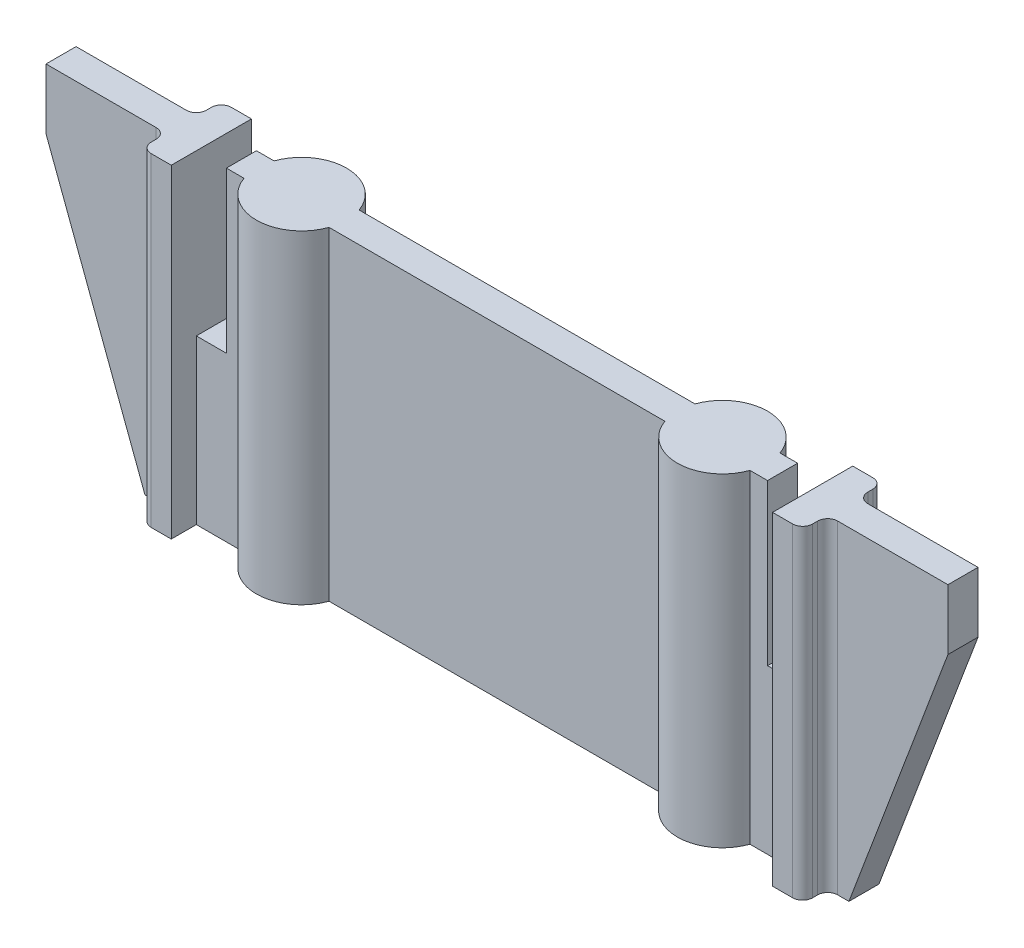
SolidWorks part; units mm, degrees
ref_plane "Front Plane" through (0, 0, 0) normal (0, 0, 1) x (1, 0, 0)
ref_plane "Top Plane" through (0, 0, 0) normal (0, 1, 0) x (1, 0, 0)
ref_plane "Right Plane" through (0, 0, 0) normal (1, 0, 0) x (0, 0, -1)
sketch "Sketch1" plane through (0, 0, 0) normal (0, 1, 0) x (1, 0, 0)
  line L0 (0, 0) -> (0, 10.4261) construction
  line L1 (-27, -17.5) -> (27, -17.5) construction
  line L2 (-27, -17.5) -> (-27, 11.1) construction
  line L3 (-27, 17.5) -> (27, 17.5) construction
  line L4 (27, -17.5) -> (27, 11.1) construction
  line L5 (-27, -17.5) -> (16.2, 10.5) construction
  line L6 (-27, 17.5) -> (-23.8664, 15.469) construction
  line L7 (-27, 11.1) -> (-27, 12.9) construction
  line L8 (-45, 13.5) -> (-25.2426, 13.5)
  line L9 (-45, 13.5) -> (-45, 10.5)
  line L10 (-45, 10.5) -> (-25.2426, 10.5)
  line L11 (45, 13.5) -> (45, 10.5)
  line L12 (-45, 13.5) -> (-25.4195, 12.8473) construction
  line L13 (-45, 10.5) -> (-25.4195, 11.1527) construction
  line L14 (-27, 12.9) -> (-27, 17.5) construction
  line L15 (-19.5181, 12.6506) -> (-16.6629, 10.8001) construction
  line L16 (-17.6087, 11.413) -> (27, -17.5) construction
  line L17 (-16.5339, 12.5511) -> (0, 12) construction
  line L18 (17.6087, 11.413) -> (16.5339, 11.4489) construction
  line L19 (0, 12) -> (16.5339, 12.5511) construction
  line L20 (25.4195, 12.8473) -> (45, 13.5) construction
  line L21 (16.6629, 10.8001) -> (19.5181, 12.6506) construction
  line L22 (19.5181, 12.6506) -> (20.8286, 13.5) construction
  line L23 (16.5339, 11.4489) -> (25.4195, 11.1527) construction
  line L24 (25.4195, 11.1527) -> (45, 10.5) construction
  line L25 (16.2, 10.5) -> (17.6087, 11.413) construction
  line L26 (17.6087, 11.413) -> (16.6629, 10.8001) construction
  line L27 (0, 12) -> (17.6087, 11.413) construction
  line L28 (-16.6629, 10.8001) -> (-17.6087, 11.413) construction
  line L29 (-25.2426, 10.5) -> (-16.7574, 10.5) construction
  line L30 (-16.7574, 10.5) -> (16.7574, 10.5)
  line L31 (-25.4195, 11.1527) -> (-16.5339, 11.4489) construction
  line L32 (-16.5339, 11.4489) -> (0, 12) construction
  line L33 (-25.4195, 12.8473) -> (-19.5181, 12.6506) construction
  line L34 (-19.5181, 12.6506) -> (-16.5339, 12.5511) construction
  line L35 (-25.2426, 13.5) -> (-20.8286, 13.5) construction
  line L36 (-16.7574, 13.5) -> (16.7574, 13.5)
  line L37 (-23.8664, 15.469) -> (-20.8286, 13.5) construction
  line L38 (-20.8286, 13.5) -> (-19.5181, 12.6506) construction
  line L39 (-20.8286, 13.5) -> (-16.7574, 13.5) construction
  line L40 (16.7574, 10.5) -> (10.6337, 10.5) construction
  line L41 (25.2426, 10.5) -> (45, 10.5)
  line L42 (16.5339, 12.5511) -> (19.5181, 12.6506) construction
  line L43 (16.7574, 13.5) -> (20.8286, 13.5) construction
  line L44 (25.2426, 13.5) -> (45, 13.5)
  line L45 (20.8286, 13.5) -> (23.8664, 15.469) construction
  line L46 (23.8664, 15.469) -> (27, 17.5) construction
  line L47 (20.8286, 13.5) -> (25.2426, 13.5) construction
  line L48 (19.5181, 12.6506) -> (45, 13.5) construction
  line L49 (27, 11.1) -> (27, 12.9) construction
  line L50 (27, 12.9) -> (27, 17.5) construction
  arc A0 (16.6629, 10.8001) -> (25.2426, 10.5) centre (21, 12) ccw construction
  arc A1 (-25.2426, 10.5) -> (-16.7574, 10.5) centre (-21, 12) ccw
  arc A2 (-25.4195, 12.8473) -> (-25.4195, 11.1527) centre (-21, 12) ccw construction
  arc A3 (-16.6629, 10.8001) -> (-16.5339, 11.4489) centre (-21, 12) ccw construction
  arc A4 (-16.7574, 13.5) -> (-25.2426, 13.5) centre (-21, 12) ccw
  arc A5 (16.5339, 12.5511) -> (16.6629, 10.8001) centre (21, 12) ccw construction
  arc A6 (16.7574, 13.5) -> (16.5339, 12.5511) centre (21, 12) ccw construction
  arc A7 (16.5339, 11.4489) -> (16.7574, 10.5) centre (21, 12) ccw construction
  arc A8 (16.7574, 10.5) -> (25.2426, 10.5) centre (21, 12) ccw
  arc A9 (-16.7574, 10.5) -> (-16.5339, 11.4489) centre (-21, 12) ccw construction
  arc A10 (-16.7574, 13.5) -> (-25.2426, 13.5) centre (-21, 12) ccw construction
  arc A11 (25.4195, 11.1527) -> (25.4195, 12.8473) centre (21, 12) ccw construction
  arc A12 (25.2426, 13.5) -> (16.7574, 13.5) centre (21, 12) ccw
  arc A13 (25.4195, 12.8473) -> (25.2426, 13.5) centre (21, 12) ccw construction
  arc A14 (25.2426, 10.5) -> (25.4195, 11.1527) centre (21, 12) ccw construction
  arc A15 (25.4195, 11.1527) -> (16.5339, 11.4489) centre (21, 12) ccw construction
  arc A16 (25.2426, 10.5) -> (25.4195, 11.1527) centre (21, 12) ccw construction
  arc A17 (-25.4195, 11.1527) -> (-25.2426, 10.5) centre (-21, 12) ccw construction
  arc A18 (-25.2426, 10.5) -> (-16.6629, 10.8001) centre (-21, 12) ccw construction
  arc A19 (-25.4195, 11.1527) -> (-25.2426, 10.5) centre (-21, 12) ccw construction
  arc A20 (-25.2426, 13.5) -> (-25.4195, 12.8473) centre (-21, 12) ccw construction
  arc A21 (-25.4195, 12.8473) -> (-25.4195, 11.1527) centre (-21, 12) ccw construction
  arc A22 (-25.2426, 13.5) -> (-25.4195, 12.8473) centre (-21, 12) ccw construction
  arc A23 (-16.5339, 11.4489) -> (-16.5339, 12.5511) centre (-21, 12) ccw construction
  arc A24 (-16.5339, 11.4489) -> (-16.5339, 12.5511) centre (-21, 12) ccw construction
  arc A25 (-16.5339, 12.5511) -> (-16.7574, 13.5) centre (-21, 12) ccw construction
  arc A26 (-16.5339, 12.5511) -> (-16.7574, 13.5) centre (-21, 12) ccw construction
  point P4 (0, 0)
  point P13 (0, 12)
  dimension "D1" = 9
  dimension "D2" = 3
  dimension "D3" = 54
  dimension "D4" = 35
  dimension "D5" = 42
  dimension "D6" = 90
  dimension "D7" = 12
extrude "Boss-Extrude1" add sketch "Sketch1" along normal blind 32.31 contours A4 L8 L9 L10 A1 L30 A8 L41 L11 L44 A12 L36
sketch "Sketch2" plane through (0, 0, -10.5) normal (0, 0, 1) x (1, 0, 0)
  line L0 (-35.1213, 0) -> (-45, 26.2724)
  line L1 (-45, 0) -> (-25.2426, 0) construction
  line L2 (-45, 32.31) -> (-45, 0) construction
  line L3 (-45, 26.2724) -> (-58.3904, 22.5254)
  line L4 (-58.3904, 22.5254) -> (-53.8147, -5.5007)
  line L5 (-53.8147, -5.5007) -> (-35.1213, -4.7634)
  line L6 (-35.1213, -4.7634) -> (-35.1213, 0)
  line L7 (0, 0) -> (0, 6.7705) construction
  line L8 (-16.7574, 0) -> (16.7574, 0) construction
  line L9 (53.8147, -5.5007) -> (35.1213, -4.7634)
  line L10 (58.3904, 22.5254) -> (53.8147, -5.5007)
  line L11 (45, 26.2724) -> (58.3904, 22.5254)
  line L12 (35.1213, 0) -> (45, 26.2724)
  line L13 (35.1213, -4.7634) -> (35.1213, 0)
extrude "Cut-Extrude1" cut sketch "Sketch2" against normal blind 25
sketch "Sketch3" plane through (0, 32.31, 0) normal (0, 1, 0) x (1, 0, 0)
  line L0 (0, 0) -> (0, 18.923) construction
  line L1 (-30, 3.9506) -> (-27, 3.9506)
  line L2 (-30, 3.9506) -> (-30, 20.1133)
  line L3 (-30, 20.1133) -> (-27, 20.1133)
  line L4 (-27, 3.9506) -> (-27, 20.1133)
  line L5 (-30, 3.9506) -> (-27, 20.1133) construction
  line L6 (-30, 20.1133) -> (-27, 3.9506) construction
  line L7 (30, 20.1133) -> (27, 20.1133)
  line L8 (27, 3.9506) -> (27, 20.1133)
  line L9 (30, 3.9506) -> (27, 3.9506)
  line L10 (30, 3.9506) -> (30, 20.1133)
  point P0 (-28.5, 12.032)
  dimension "D1" = 3
  dimension "D2" = 60
extrude "Cut-Extrude2" cut sketch "Sketch3" against normal blind 16
sketch "Sketch4" plane through (0, 0, 0) normal (0, -1, 0) x (1, 0, 0)
  line L1 (-33, -16) -> (-30, -16)
  line L2 (-33, -16) -> (-33, -8)
  line L3 (-33, -8) -> (-30, -8)
  line L4 (-30, -16) -> (-30, -8)
  line L5 (-33, -16) -> (-30, -8) construction
  line L6 (-33, -8) -> (-30, -16) construction
  line L7 (-35.1213, -12) -> (-14.4349, -12) construction
  line L8 (-35.1213, -10.5) -> (-35.1213, -13.5) construction
  line L9 (-30, -13.5) -> (-30, -10.5) construction
  point P0 (-31.5, -12)
  dimension "D1" = 3
  dimension "D2" = 8
extrude "Boss-Extrude2" add sketch "Sketch4" against normal up to surface (32.31 mm away) up to face at (-37.5, 32.31, -12)
fillet "Fillet1" radius 1 4 edges at (-33, 16.155, -16) (-33, 16.155, -8) (-33, 16.155, -10.5) (-33, 16.155, -13.5)
mirror "Mirror1" about plane through (0, 0, 0) normal (1, 0, 0) of "Boss-Extrude2"
fillet "Fillet2" radius 1 4 edges at (33, 16.155, -16) (33, 16.155, -13.5) (33, 16.155, -10.5) (33, 16.155, -8)
hole_wizard "M3 Clearance Hole1" positions "Sketch5" profile "Sketch6" hole size "M3" standard "ANSI Metric"
sketch "Sketch5" plane through (0, 0, 0) normal (0, -1, 0) x (-1, 0, 0)
  circle A0 centre (-21, 12) radius 5.6035 construction
  arc A1 (-16.7574, 13.5) -> (-25.2426, 13.5) centre (-21, 12) ccw construction
  arc A2 (25.2426, 13.5) -> (16.7574, 13.5) centre (21, 12) ccw construction
  point P0 (-21, 12)
  point P2 (21, 12)
sketch "Sketch6" plane through (21, 0, -12) normal (1, 0, 0) x (0, 0, -1)
  line L0 (0, 0) -> (0, 17.0815)
  line L1 (0, 17.0815) -> (1.8, 16)
  line L2 (1.8, 16) -> (1.8, 0)
  line L5 (1.8, 0) -> (0, 0)
  line L10 (0, 17.0815) -> (-1.8, 16) construction
  line L11 (0, -6.35) -> (0, 107.95) construction
  dimension "Hole Dia." = 3.6
  dimension "Hole Depth" = 16
  dimension "Drill Angle" = 118
ref_plane "Plane1" through (0, 10, 0) normal (0, -1, 0) x (-1, 0, 0)
sketch "Sketch7" plane through (0, 10, 0) normal (0, -1, 0) x (-1, 0, 0)
  line L1 (-21, 15.6373) -> (-24.15, 13.8187) construction
  line L2 (-24.15, 13.8187) -> (-24.15, 10.1813)
  line L3 (-24.15, 10.1813) -> (-21, 8.3627)
  line L4 (-21, 8.3627) -> (-17.85, 10.1813)
  line L5 (-17.85, 10.1813) -> (-17.85, 13.8187)
  line L6 (-17.85, 13.8187) -> (-21, 15.6373) construction
  line L7 (-24.15, 13.8187) -> (-17.85, 13.8187) construction
  line L8 (-24.15, 13.8187) -> (-24.15, 20.1574)
  line L9 (-24.15, 20.1574) -> (-17.85, 20.1574)
  line L10 (-17.85, 13.8187) -> (-17.85, 20.1574)
  circle A0 centre (-21, 12) radius 3.15 construction
  dimension "D1" = 6.3
extrude "Cut-Extrude3" cut sketch "Sketch7" along normal blind 4
mirror "Mirror2" about plane through (0, 0, 0) normal (1, 0, 0) of "Cut-Extrude3"
